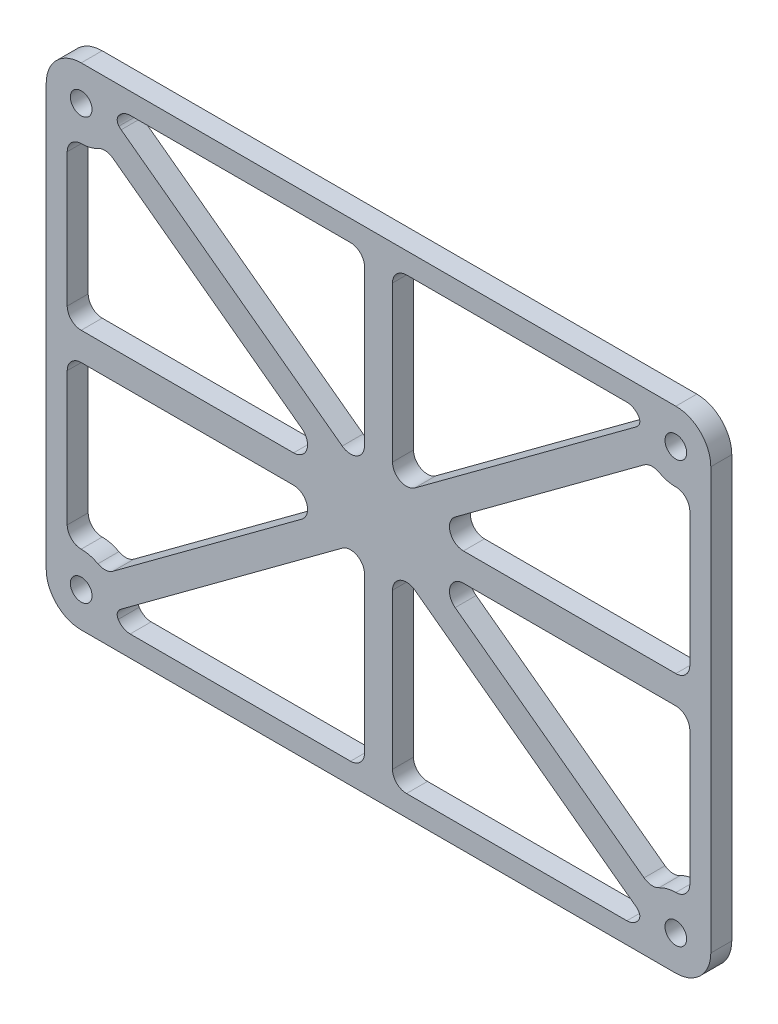
SolidWorks part; units mm, degrees
material "Thornel Mat VMA"
ref_plane "前视基准面" through (0, 0, 0) normal (0, 0, 1) x (1, 0, 0)
ref_plane "上视基准面" through (0, 0, 0) normal (0, 1, 0) x (1, 0, 0)
ref_plane "右视基准面" through (0, 0, 0) normal (1, 0, 0) x (0, 0, -1)
sketch "草图1" plane through (0, 0, 0) normal (0, 0, 1) x (1, 0, 0)
  line L0 (0, 0) -> (-50000, 0) construction
  line L1 (47.5, -35.1) -> (-47.5, -35.1)
  line L2 (47.5, -35.1) -> (47.5, 35.1)
  line L3 (47.5, 35.1) -> (-47.5, 35.1)
  line L4 (-47.5, -35.1) -> (-47.5, 35.1)
  line L5 (47.5, -35.1) -> (-47.5, 35.1) construction
  line L6 (47.5, 35.1) -> (-47.5, -35.1) construction
  line L7 (0, 0) -> (0, 50000) construction
  line L8 (-44.5, -2) -> (-44.5, -25.5174)
  line L9 (-6.0719, -2) -> (-39.1168, -26.4184)
  line L10 (-44.5, -2) -> (-6.0719, -2)
  line L11 (-6.0719, 2) -> (-39.1168, 26.4184)
  line L12 (-44.5, 2) -> (-6.0719, 2)
  line L13 (-44.5, 2) -> (-44.5, 25.5174)
  line L14 (-2, 32.1) -> (-37.9174, 32.1)
  line L15 (-2, 3.9647) -> (-37.501, 30.198)
  line L16 (-2, 3.9647) -> (-2, 32.1)
  line L17 (-2, -3.9647) -> (-2, -32.1)
  line L18 (-2, -32.1) -> (-37.9174, -32.1)
  line L19 (-2, -3.9647) -> (-37.501, -30.198)
  line L20 (2, -32.1) -> (37.9174, -32.1)
  line L21 (2, -3.9647) -> (2, -32.1)
  line L22 (2, -3.9647) -> (37.501, -30.198)
  line L23 (6.0719, -2) -> (39.1168, -26.4184)
  line L24 (44.5, -2) -> (6.0719, -2)
  line L25 (44.5, -2) -> (44.5, -25.5174)
  line L26 (44.5, 2) -> (6.0719, 2)
  line L27 (6.0719, 2) -> (39.1168, 26.4184)
  line L28 (44.5, 2) -> (44.5, 25.5174)
  line L29 (2, 3.9647) -> (2, 32.1)
  line L30 (2, 3.9647) -> (37.501, 30.198)
  line L31 (2, 32.1) -> (37.9174, 32.1)
  circle A0 centre (-42.5, 30.1) radius 1.55
  circle A2 centre (42.5, 30.1) radius 1.55
  circle A3 centre (42.5, -30.1) radius 1.55
  circle A4 centre (-42.5, -30.1) radius 1.55
  circle A5 centre (-42.5, 30.1) radius 5
  circle A6 centre (-42.5, -30.1) radius 5
  circle A7 centre (42.5, -30.1) radius 5
  circle A8 centre (42.5, 30.1) radius 5
  point P0 (0, 0)
  dimension "D1" = 3.1
  dimension "D5" = 5
  dimension "D6" = 10
  dimension "D2" = 85
  dimension "D3" = 60.2
  dimension "D4" = 5
  dimension "D7" = 2
  dimension "D8" = 3
  dimension "D9" = 4
  dimension "D10" = 3
  dimension "D11" = 2
extrude "凸台-拉伸1" add sketch "草图1" along normal blind 3 contours A8 L3 A5 L14 L16 L15 L11 L12 L13 L4 A6 L8 L10 L9 L19 L17 L18 L1 A7 L20 L21 L22 L23 L24 L25 L2 L28 L26 L27 L30 L29 L31 | A5 A0 | A8 A2 | A7 A3 | A6 A4 region at (0, 0, 0) region at (39.8388, -34.165, 0) region at (-45.9355, -33.5355, 0) region at (46.565, 27.4388, 0) region at (-45.9355, 33.5355, 0)
fillet "圆角1" radius 2 32 edges at (39.1168, 26.4184, 1.5) (6.0719, 2, 1.5) (44.5, 2, 1.5) (44.5, 25.5174, 1.5) (44.5, -25.5174, 1.5) (44.5, -2, 1.5) (6.0719, -2, 1.5) (39.1168, -26.4184, 1.5) (2, -3.9647, 1.5) (2, -32.1, 1.5) (37.9174, -32.1, 1.5) (37.501, -30.198, 1.5) (-37.9174, -32.1, 1.5) (-2, -32.1, 1.5) (-2, -3.9647, 1.5) (-37.501, -30.198, 1.5) (-6.0719, -2, 1.5) (-44.5, -2, 1.5) (-44.5, -25.5174, 1.5) (-39.1168, -26.4184, 1.5) (-44.5, 25.5174, 1.5) (-6.0719, 2, 1.5) (-39.1168, 26.4184, 1.5) (-2, 3.9647, 1.5) (-2, 32.1, 1.5) (-37.9174, 32.1, 1.5) (-37.501, 30.198, 1.5) (2, 32.1, 1.5) (2, 3.9647, 1.5) (37.501, 30.198, 1.5) (37.9174, 32.1, 1.5) (-44.5, 2, 1.5)
fillet "圆角2" radius 1 4 edges at (-37.4536, 30.5285, 1.5) (-37.4536, -30.5285, 1.5) (37.4536, -30.5285, 1.5) (37.4536, 30.5285, 1.5)
